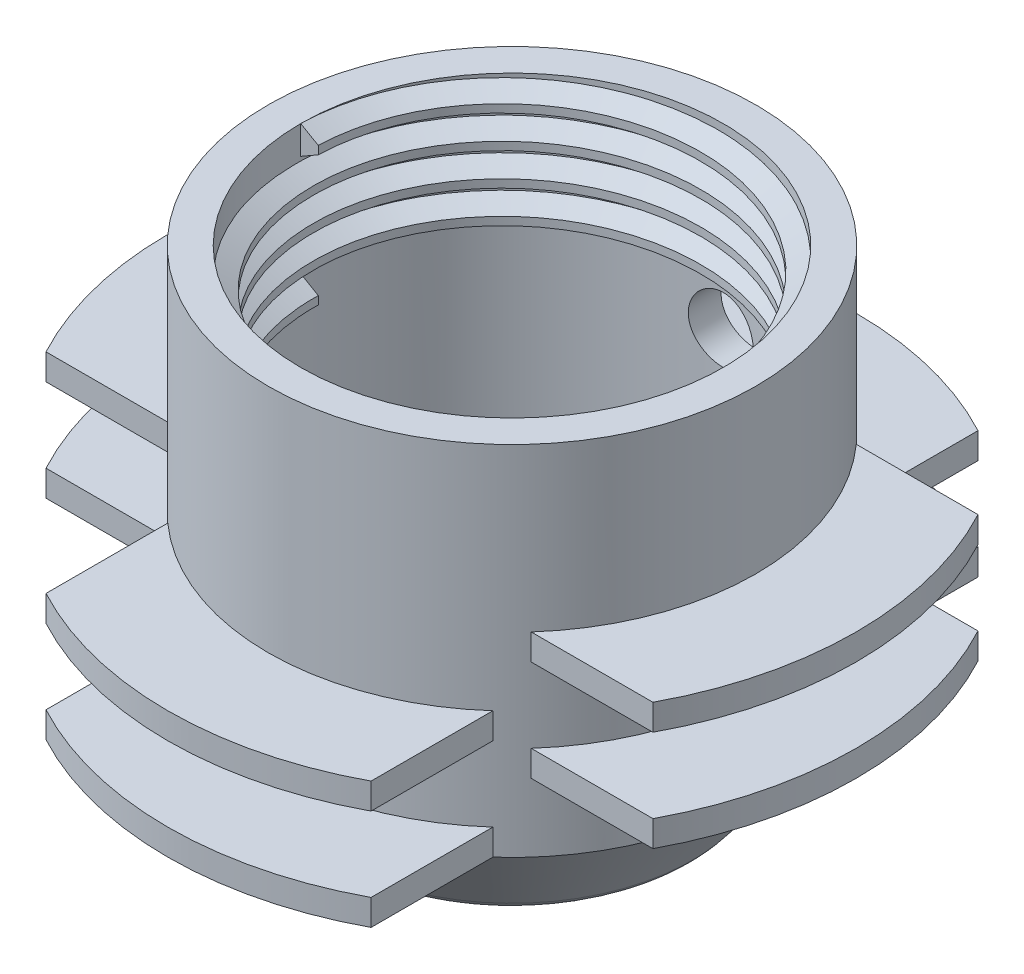
SolidWorks part; units mm, degrees
ref_plane "Front Plane" through (0, 0, 0) normal (0, 0, 1) x (1, 0, 0)
ref_plane "Top Plane" through (0, 0, 0) normal (0, 1, 0) x (1, 0, 0)
ref_plane "Right Plane" through (0, 0, 0) normal (1, 0, 0) x (0, 0, -1)
sketch "Sketch1" plane through (0, 0, 0) normal (0, 1, 0) x (1, 0, 0)
  circle A0 centre (0, 0) radius 7.5
  dimension "D1" = 15
extrude "Boss-Extrude1" add sketch "Sketch1" along normal blind 11
sketch "Sketch2" plane through (0, 11, 0) normal (0, 1, 0) x (1, 0, 0)
  circle A0 centre (0, 0) radius 6.5
  circle A1 centre (0, 0) radius 7.5 construction
extrude "Cut-Extrude1" cut sketch "Sketch2" against normal through all both and the other way through all
ref_plane "Plane2" through (0, 6, 0) normal (0, 1, 0) x (1, 0, 0)
sketch "Sketch3" plane through (0, 6, 0) normal (0, 1, 0) x (1, 0, 0)
  line L1 (10.5902, -5) -> (5.5902, -5)
  line L2 (10.5902, -5) -> (10.5902, 5)
  line L3 (10.5902, 5) -> (5.5902, 5)
  line L4 (5.5902, -5) -> (5.5902, 5)
  line L5 (10.5902, -5) -> (5.5902, 5) construction
  line L6 (10.5902, 5) -> (5.5902, -5) construction
  circle A0 centre (0, 0) radius 7.5 construction
  arc A1 (9.3355, -5) -> (9.3355, 5) centre (0, 0) ccw
  circle A2 centre (0, 0) radius 6.5 construction
  arc A3 (5.5902, 5) -> (5.5902, -5) centre (0, 0) cw
  point P0 (8.0902, 0)
  dimension "D1" = 10
  dimension "D2" = 5
extrude "Boss-Extrude2" add sketch "Sketch3" against normal blind 3.9 contours L1 A1 L3 region at (8.5149, 6, 0)
sketch "Sketch4" plane through (0, 0, 0) normal (0, 0, 1) x (1, 0, 0)
  line L1 (7.5, 2.9) -> (10.5902, 2.9)
  line L2 (7.5, 2.9) -> (7.5, 5.2)
  line L3 (7.5, 5.2) -> (10.5902, 5.2)
  line L4 (10.5902, 2.9) -> (10.5902, 5.2)
  line L5 (7.5, 2.9) -> (10.5902, 5.2) construction
  line L6 (7.5, 5.2) -> (10.5902, 2.9) construction
  line L7 (5.5902, 2.1) -> (5.5902, 6) construction
  line L8 (0, 0) -> (0, 11) construction
  line L9 (6.5, 11) -> (-6.5, 11) construction
  line L10 (10.5902, 2.1) -> (10.5902, 6) construction
  point P0 (9.0451, 4.05)
  point P9 (5.5902, 4.05)
  dimension "D1" = 2.3
  dimension "D2" = 7.5
revolve "Cut-Revolve3" cut sketch "Sketch4" angle 90 mid plane about L8
mirror "Mirror1" about plane through (0, 0, 0) normal (1, 0, 0) of "Boss-Extrude2", "Cut-Revolve3"
sketch "Sketch5" plane through (0, 2.9, 0) normal (0, 1, 0) x (1, 0, 0)
  line L1 (-5, -10.5902) -> (5, -10.5902)
  line L2 (-5, -10.5902) -> (-5, -5.5902)
  line L3 (-5, -5.5902) -> (5, -5.5902)
  line L4 (5, -10.5902) -> (5, -5.5902)
  line L5 (-5, -10.5902) -> (5, -5.5902) construction
  line L6 (-5, -5.5902) -> (5, -10.5902) construction
  circle A0 centre (0, 0) radius 7.5 construction
  arc A1 (-5, -9.3355) -> (5, -9.3355) centre (0, 0) ccw
  arc A2 (-5, -5.5902) -> (5, -5.5902) centre (0, 0) ccw
  point P0 (0, -8.0902)
  dimension "D1" = 10
  dimension "D2" = 5
extrude "Boss-Extrude3" add sketch "Sketch5" against normal blind 2.9 and the other way blind 1 contours A1 L4 L3 L2 region at (0, 2.9, 8.5149)
sketch "Sketch6" plane through (0, 0, 0) normal (1, 0, 0) x (0, 0, -1)
  line L0 (-5.5902, 0) -> (-5.5902, 3.9) construction
  line L1 (-7.5, 0.8) -> (-10.5902, 0.8)
  line L2 (-7.5, 0.8) -> (-7.5, 3.1)
  line L3 (-7.5, 3.1) -> (-10.5902, 3.1)
  line L4 (-10.5902, 0.8) -> (-10.5902, 3.1)
  line L5 (-7.5, 0.8) -> (-10.5902, 3.1) construction
  line L6 (-7.5, 3.1) -> (-10.5902, 0.8) construction
  line L7 (-10.5902, 3.9) -> (-10.5902, 0) construction
  line L8 (0, 0) -> (0, 6) construction
  point P0 (-9.0451, 1.95)
  point P7 (-5.5902, 1.95)
  dimension "D1" = 7.5
  dimension "D2" = 2.3
revolve "Cut-Revolve4" cut sketch "Sketch6" angle 90 mid plane about L8 region at (0, 1.95, 9.0451)
mirror "Mirror2" about plane through (0, 0, 0) normal (0, 0, 1) of "Cut-Revolve4", "Boss-Extrude3"
sketch "Sketch22" plane through (0, 0, 0) normal (0, 0, 1) x (1, 0, 0)
  line L0 (7.5, 11) -> (-7.5, 11) construction
  circle A0 centre (0, 5.5) radius 1
  dimension "D1" = 2
  dimension "D2" = 5.5
extrude "Cut-Extrude2" cut sketch "Sketch22" against normal up to surface (7.433 mm away) up to face at (0, 0.4, 0)
sketch "Sketch23" plane through (0, 0, 0) normal (0, 0, 1) x (1, 0, 0)
  line L0 (7.5, 0) -> (6.25, 0)
  line L1 (0, 0) -> (0, 11) construction
  line L2 (7.5, 0) -> (5.25, -3)
  line L3 (6.25, 0) -> (4, -3)
  line L4 (5.25, -3) -> (4, -3)
  line L5 (-7.5, 0) -> (7.5, 0) construction
  line L6 (7.5, 11) -> (-7.5, 11) construction
  line L8 (3.5, -3) -> (4.75, -3)
  line L9 (3.5, -3) -> (3.5, -2)
  line L10 (3.5, -2) -> (4.75, -2)
  line L11 (4.75, -3) -> (4.75, -2)
  dimension "D1" = 3
  dimension "D2" = 4
  dimension "D4" = 0.5
  dimension "D5" = 1
  dimension "D3" = 1
revolve "Revolve1" add sketch "Sketch23" angle 360 about L1 region at (5.8889, -1.3704, 0) region at (4.5, -2.6667, 0) region at (3.9643, -2.4286, 0)
thread "Thread1" pitch 1 method extrude profile "Thread Profile2" start angle 0, offset 0, length 4, pitch 1, diameter 13
ref_plane "Plane4" through (-6.5, 11, 0) normal (0, 0, 1) x (-1, 0, 0)
sketch "Thread Profile2" plane through (-6.5, 11, 0) normal (0, 0, 1) x (-1, 0, 0)
  line L0 (0, 0) -> (0, 1) construction
  line L11 (0, 0) -> (0, 0.875)
  line L12 (0, 0.875) -> (-0.5413, 0.5625)
  line L13 (-0.5413, 0.5625) -> (-0.5413, 0.3125)
  line L15 (-0.5413, 0.3125) -> (0, 0)
  line L17 (-0.5413, 0.4375) -> (0, 0.4375) construction
  point P2 (0, 0)
  dimension "Pitch" = 1
  dimension "Profile_Angle" = 60
  dimension "Profile_Land" = 0.25
  dimension "Profile_Height" = 0.5413
fillet "Fillet2" radius 1 1 edges at (0, -3, -5.25)
equation "\"diameter_electrode_outer\"= 15mm"
equation "\"height_electrode_straigth\"= \"height_frame\" * 2 + \"height_wing_individual\" * 2 + \"height_thread\" + 1mm"
equation "\"width_wall\"= 1mm"
equation "\"width_wing\"= 5mm"
equation "\"length_wing\"= 10mm"
equation "\"height_wing_individual\"= 1mm"
equation "\"height_frame\"= 2mm"
equation "\"offset\"= 0.1mm"
equation "\"height_wing_total\"= \"height_wing_individual\" * 2 + \"height_frame\" - \"offset\""
equation "\"D1@Sketch1\"=\"diameter_electrode_outer\""
equation "\"D1@Boss-Extrude1\"=\"height_electrode_straigth\""
equation "\"D1@Sketch2\"=\"width_wall\""
equation "\"D1@Sketch3\"=\"length_wing\""
equation "\"D2@Sketch3\"=\"width_wing\""
equation "\"D1@Boss-Extrude2\"=\"height_wing_total\""
equation "\"D1@Sketch4\"=\"height_wing_gap\""
equation "\"D2@Sketch4\"=\"diameter_electrode_outer\"/2"
equation "\"D1@Sketch5\"=\"length_wing\""
equation "\"D2@Sketch5\"=\"width_wing\""
equation "\"D1@Boss-Extrude3\"=\"height_wing_total\"-\"height_wing_individual\""
equation "\"D1@Sketch6\"=\"diameter_electrode_outer\"/2"
equation "\"D2@Sketch6\"=\"height_wing_gap\""
equation "\"D2@Boss-Extrude3\"=\"height_wing_individual\""
equation "\"width_cotton_holder\"= 0.5mm"
equation "\"height_cotton_holder\"= 1mm"
equation "\"width_thread\"= 1mm"
equation "\"height_thread\"= 4mm"
equation "\"pitch_thread_large\"= 1mm"
equation "\"pitch_thread_small\"= 0.1mm"
equation "\"diameter_tube\"= 2mm"
equation "\"D1@Sketch22\"=\"diameter_tube\""
equation "\"D2@Sketch22\"=\"diameter_tube\"/2+\"height_thread\"+0.5mm"
equation "\"height_electrode_chamfer\"= 3mm"
equation "\"D1@Sketch23\"=\"height_electrode_chamfer\""
equation "\"diameter_electrode_tip_in\"= 8mm"
equation "\"D2@Sketch23\"=\"diameter_electrode_tip_in\"/2"
equation "\"D4@Thread1\"=\"height_thread\""
equation "\"D4@Sketch23\"=\"width_cotton_holder\""
equation "\"D5@Sketch23\"=\"height_cotton_holder\""
equation "\"D3@Sketch23\"=\"width_wall\""
equation "\"D1@Fillet2\"=\"width_wall\""
equation "\"width_dupont\"= 2mm"
equation "\"height_dupont\"= 1.7mm"
equation "\"length_dupont\"= 11.5mm"
equation "\"height_wing_gap\"= \"height_frame\" + \"offset\" * 3"
